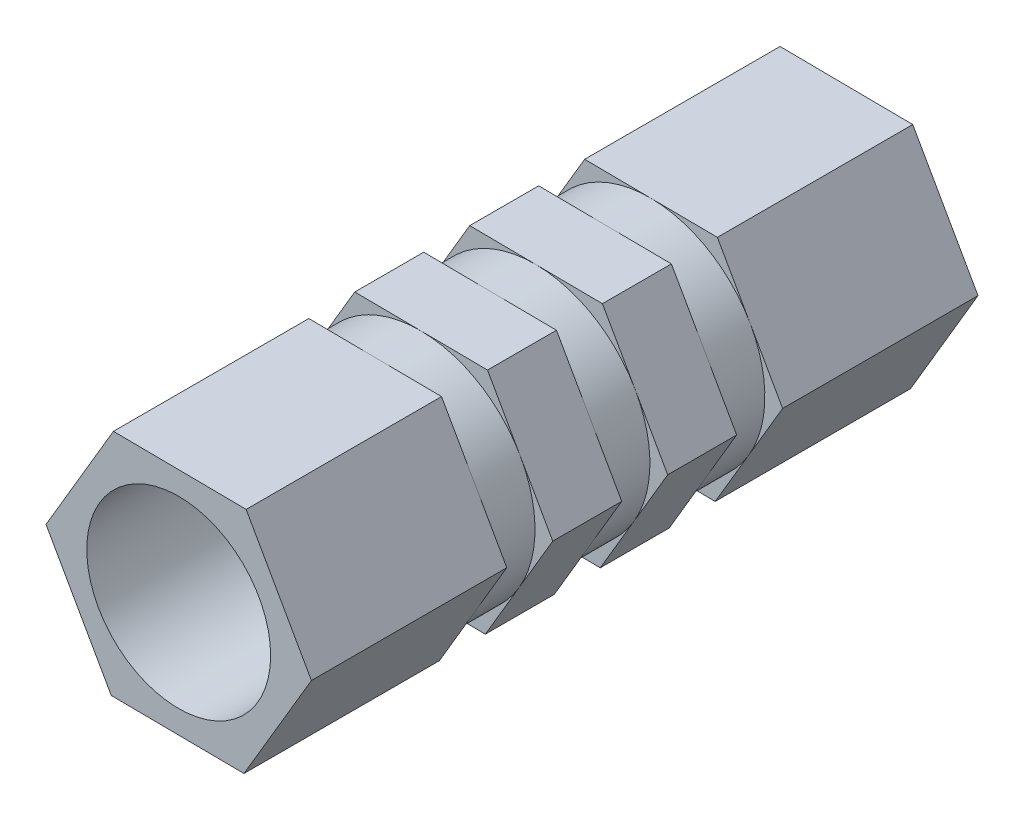
SolidWorks part; units mm, degrees
ref_plane "Front Plane" through (0, 0, 0) normal (0, 0, 1) x (1, 0, 0)
ref_plane "Top Plane" through (0, 0, 0) normal (0, 1, 0) x (1, 0, 0)
ref_plane "Right Plane" through (0, 0, 0) normal (1, 0, 0) x (0, 0, -1)
sketch "Sketch1" plane through (0, 0, 0) normal (0, 0, 1) x (1, 0, 0)
  line L1 (1.467, 2.4862) -> (-1.4196, 2.5136)
  line L2 (-1.4196, 2.5136) -> (-2.8866, 0.0273)
  line L3 (-2.8866, 0.0273) -> (-1.467, -2.4862)
  line L4 (-1.467, -2.4862) -> (1.4196, -2.5136)
  line L5 (1.4196, -2.5136) -> (2.8866, -0.0273)
  line L6 (2.8866, -0.0273) -> (1.467, 2.4862)
  circle A0 centre (0, 0) radius 2.5 construction
  circle A1 centre (0, 0) radius 2
  circle A2 centre (0, 0) radius 2.5
extrude "Boss-Extrude1" add sketch "Sketch1" along normal blind 4.25 contours A2 A1 | A2 L1 L2 | A2 L6 L1 | A2 L5 L6 | A2 L4 L5 | A2 L3 L4 | A2 L2 L3 region at (1.3131, 2.2254, 0) region at (-1.2707, 2.2499, 0) region at (1.2345, 2.0922, 0) region at (2.5838, -0.0245, 0) region at (-2.5838, 0.0245, 0) region at (-1.3131, -2.2254, 0) region at (1.2707, -2.2499, 0)
sketch "Sketch2" plane through (0, 0, 4.25) normal (0, 0, 1) x (1, 0, 0)
  line L0 (1.467, 2.4862) -> (-1.4196, 2.5136)
  line L1 (-1.4196, 2.5136) -> (-2.8866, 0.0273)
  line L2 (-2.8866, 0.0273) -> (-1.467, -2.4862)
  line L3 (-1.467, -2.4862) -> (1.4196, -2.5136)
  line L4 (1.4196, -2.5136) -> (2.8866, -0.0273)
  line L5 (2.8866, -0.0273) -> (1.467, 2.4862)
  circle A0 centre (0, 0) radius 2.5 construction
  circle A1 centre (0, 0) radius 2
  circle A2 centre (0, 0) radius 2.5
  circle M7 centre (0, 0) radius 2
extrude "Boss-Extrude2" add sketch "Sketch2" along normal blind 1 contours A2 M7 region at (1.2345, 2.0922, 4.25)
sketch "Sketch3" plane through (0, 0, 5.25) normal (0, 0, 1) x (1, 0, 0)
  line L0 (1.467, 2.4862) -> (-1.4196, 2.5136)
  line L1 (-1.4196, 2.5136) -> (-2.8866, 0.0273)
  line L2 (-2.8866, 0.0273) -> (-1.467, -2.4862)
  line L3 (-1.467, -2.4862) -> (1.4196, -2.5136)
  line L4 (1.4196, -2.5136) -> (2.8866, -0.0273)
  line L5 (2.8866, -0.0273) -> (1.467, 2.4862)
  circle A0 centre (0, 0) radius 2.5 construction
  circle A1 centre (0, 0) radius 2
  circle A2 centre (0, 0) radius 2.5
  circle M1 centre (0, 0) radius 2
  circle M2 centre (0, 0) radius 2.5
extrude "Boss-Extrude3" add sketch "Sketch3" along normal blind 1.5 contours M2 M1 | L0 L1 M2 | L5 L0 M2 | L4 L5 M2 | L3 L4 M2 | L2 L3 M2 | L1 L2 M2 region at (1.3131, 2.2254, 5.25) region at (-1.2707, 2.2499, 5.25) region at (1.2345, 2.0922, 5.25) region at (2.5838, -0.0245, 5.25) region at (-2.5838, 0.0245, 5.25) region at (-1.3131, -2.2254, 5.25) region at (1.2707, -2.2499, 5.25)
sketch "Sketch4" plane through (0, 0, 6.75) normal (0, 0, 1) x (1, 0, 0)
  line L0 (1.467, 2.4862) -> (-1.4196, 2.5136)
  line L1 (-1.4196, 2.5136) -> (-2.8866, 0.0273)
  line L2 (-2.8866, 0.0273) -> (-1.467, -2.4862)
  line L3 (-1.467, -2.4862) -> (1.4196, -2.5136)
  line L4 (1.4196, -2.5136) -> (2.8866, -0.0273)
  line L5 (2.8866, -0.0273) -> (1.467, 2.4862)
  circle A0 centre (0, 0) radius 2.5 construction
  circle A1 centre (0, 0) radius 2
  circle A2 centre (0, 0) radius 2.5
  circle M7 centre (0, 0) radius 2
extrude "Boss-Extrude4" add sketch "Sketch4" along normal blind 1 contours A2 M7 region at (1.2345, 2.0922, 6.75)
sketch "Sketch5" plane through (0, 0, 7.75) normal (0, 0, 1) x (1, 0, 0)
  line L0 (1.467, 2.4862) -> (-1.4196, 2.5136)
  line L1 (-1.4196, 2.5136) -> (-2.8866, 0.0273)
  line L2 (-2.8866, 0.0273) -> (-1.467, -2.4862)
  line L3 (-1.467, -2.4862) -> (1.4196, -2.5136)
  line L4 (1.4196, -2.5136) -> (2.8866, -0.0273)
  line L5 (2.8866, -0.0273) -> (1.467, 2.4862)
  circle A0 centre (0, 0) radius 2.5 construction
  circle A1 centre (0, 0) radius 2
  circle A2 centre (0, 0) radius 2.5
  circle M1 centre (0, 0) radius 2
  circle M2 centre (0, 0) radius 2.5
extrude "Boss-Extrude5" add sketch "Sketch5" along normal blind 1.5 contours M2 M1 | L0 L1 M2 | L1 L2 M2 | L5 L0 M2 | L4 L5 M2 | L3 L4 M2 | L2 L3 M2 region at (1.3131, 2.2254, 7.75) region at (-1.2707, 2.2499, 7.75) region at (1.2345, 2.0922, 7.75) region at (2.5838, -0.0245, 7.75) region at (-2.5838, 0.0245, 7.75) region at (-1.3131, -2.2254, 7.75) region at (1.2707, -2.2499, 7.75)
sketch "Sketch6" plane through (0, 0, 9.25) normal (0, 0, 1) x (1, 0, 0)
  line L0 (1.467, 2.4862) -> (-1.4196, 2.5136)
  line L1 (-1.4196, 2.5136) -> (-2.8866, 0.0273)
  line L2 (-2.8866, 0.0273) -> (-1.467, -2.4862)
  line L3 (-1.467, -2.4862) -> (1.4196, -2.5136)
  line L4 (1.4196, -2.5136) -> (2.8866, -0.0273)
  line L5 (2.8866, -0.0273) -> (1.467, 2.4862)
  circle A0 centre (0, 0) radius 2.5 construction
  circle A1 centre (0, 0) radius 2
  circle A2 centre (0, 0) radius 2.5
  circle M7 centre (0, 0) radius 2
extrude "Boss-Extrude6" add sketch "Sketch6" along normal blind 1 contours A2 M7 region at (1.2345, 2.0922, 9.25)
sketch "Sketch7" plane through (0, 0, 10.25) normal (0, 0, 1) x (1, 0, 0)
  line L0 (1.467, 2.4862) -> (-1.4196, 2.5136)
  line L1 (-1.4196, 2.5136) -> (-2.8866, 0.0273)
  line L2 (-2.8866, 0.0273) -> (-1.467, -2.4862)
  line L3 (-1.467, -2.4862) -> (1.4196, -2.5136)
  line L4 (1.4196, -2.5136) -> (2.8866, -0.0273)
  line L5 (2.8866, -0.0273) -> (1.467, 2.4862)
  circle A0 centre (0, 0) radius 2.5 construction
  circle A1 centre (0, 0) radius 2
  circle A2 centre (0, 0) radius 2.5
  circle M1 centre (0, 0) radius 2
  circle M2 centre (0, 0) radius 2.5
extrude "Boss-Extrude7" add sketch "Sketch7" along normal blind 4.25 contours M2 M1 | L0 L1 M2 | L5 L0 M2 | L4 L5 M2 | L3 L4 M2 | L1 L2 M2 | L2 L3 M2 region at (1.3131, 2.2254, 10.25) region at (-1.2707, 2.2499, 10.25) region at (1.2345, 2.0922, 10.25) region at (2.5838, -0.0245, 10.25) region at (-2.5838, 0.0245, 10.25) region at (-1.3131, -2.2254, 10.25) region at (1.2707, -2.2499, 10.25)
